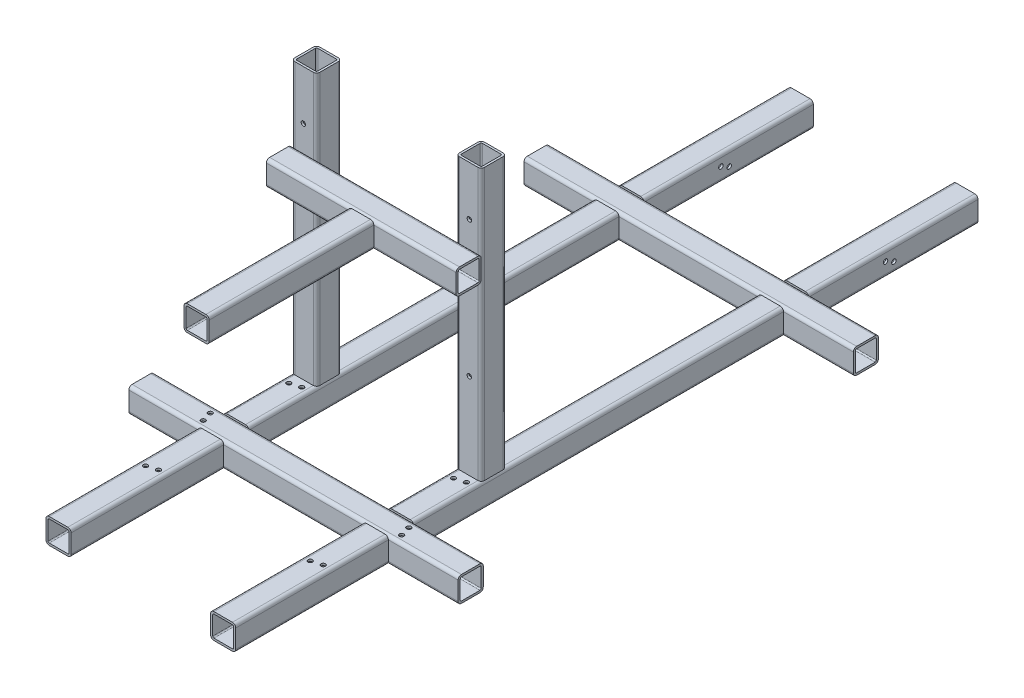
SolidWorks part; units mm, degrees
material "Alumina"
ref_plane "Front Plane" through (0, 0, 0) normal (0, 0, 1) x (1, 0, 0)
ref_plane "Top Plane" through (0, 0, 0) normal (0, 1, 0) x (1, 0, 0)
ref_plane "Right Plane" through (0, 0, 0) normal (1, 0, 0) x (0, 0, -1)
ref_plane "Bottom Face" through (0, 0, 0) normal (0, 1, 0) x (1, 0, 0)
ref_plane "Top Face" through (0, 38.1, 0) normal (0, 1, 0) x (1, 0, 0)
ref_plane "Mid Plane" through (0, 19.05, 0) normal (0, 1, 0) x (1, 0, 0)
ref_plane "Front Face" through (0, 0, 500) normal (0, 0, 1) x (1, 0, 0)
ref_plane "Back Face" through (0, 0, -500) normal (0, 0, 1) x (1, 0, 0)
ref_plane "Left Face" through (250, 0, 0) normal (1, 0, 0) x (0, 0, -1)
ref_plane "Right Face" through (-250, 0, 0) normal (1, 0, 0) x (0, 0, -1)
ref_plane "Divider Plane" through (0, 0, 140) normal (0, 0, 1) x (1, 0, 0)
ref_plane "Max Height Plane" through (0, 450, 0) normal (0, 1, 0) x (1, 0, 0)
ref_plane "Electronics Box Plane" through (0, 338.1, 0) normal (0, 1, 0) x (1, 0, 0)
sketch "Sketch2" plane through (250, 0, 0) normal (1, 0, 0) x (0, 0, -1)
  line L0 (330, 38.1) -> (-330, 38.1) construction
  line L5 (330, 0) -> (-330, 0) construction
  line L6 (0, 220) -> (0, -220) construction
  line L7 (-314.05, 38.1) -> (-285.95, 38.1)
  line L8 (-280.95, 33.1) -> (-280.95, 5)
  line L9 (-315.875, 33.1) -> (-315.875, 5)
  line L10 (-314.05, 3.175) -> (-285.95, 3.175)
  line L11 (-285.95, 0) -> (-314.05, 0)
  line L12 (-319.05, 5) -> (-319.05, 33.1)
  line L13 (-300, 38.1) -> (-300, 0) construction
  line L14 (-319.05, 19.05) -> (-280.95, 19.05) construction
  line L15 (-284.125, 5) -> (-284.125, 33.1)
  line L16 (-285.95, 34.925) -> (-314.05, 34.925)
  line L17 (-300, 34.925) -> (-300, 3.175) construction
  line L18 (-315.875, 19.05) -> (-284.125, 19.05) construction
  arc A0 (-285.95, 38.1) -> (-280.95, 33.1) centre (-285.95, 33.1) cw
  arc A1 (-280.95, 5) -> (-285.95, 0) centre (-285.95, 5) cw
  arc A2 (-314.05, 0) -> (-319.05, 5) centre (-314.05, 5) cw
  arc A3 (-319.05, 33.1) -> (-314.05, 38.1) centre (-314.05, 33.1) cw
  arc A4 (-315.875, 5) -> (-314.05, 3.175) centre (-314.05, 5) ccw
  arc A5 (-285.95, 3.175) -> (-284.125, 5) centre (-285.95, 5) ccw
  arc A6 (-284.125, 33.1) -> (-285.95, 34.925) centre (-285.95, 33.1) ccw
  arc A7 (-314.05, 34.925) -> (-315.875, 33.1) centre (-314.05, 33.1) ccw
  point P20 (-300, 19.05)
  point P39 (-300, 19.05)
  dimension "D1" = 5
  dimension "D2" = 300
  dimension "D3" = 3.175
extrude "Front Cross-Car Member" add sketch "Sketch2" against normal up to surface (500 mm away) up to plane "Right Face"
sketch "Sketch5" plane through (250, 0, 0) normal (1, 0, 0) x (0, 0, -1)
  line L0 (285.95, 38.1) -> (314.05, 38.1)
  line L1 (319.05, 33.1) -> (319.05, 5)
  line L2 (314.05, 0) -> (285.95, 0)
  line L3 (280.95, 5) -> (280.95, 33.1)
  line L4 (300, 38.1) -> (300, 0) construction
  line L5 (280.95, 19.05) -> (319.05, 19.05) construction
  line L6 (285.95, 34.925) -> (314.05, 34.925)
  line L7 (315.875, 33.1) -> (315.875, 5)
  line L8 (314.05, 3.175) -> (285.95, 3.175)
  line L9 (284.125, 5) -> (284.125, 33.1)
  line L10 (300, 34.925) -> (300, 3.175) construction
  line L11 (284.125, 19.05) -> (315.875, 19.05) construction
  line L12 (330, 0) -> (-330, 0) construction
  line L14 (330, 38.1) -> (-330, 38.1) construction
  line L15 (0, 220) -> (0, -220) construction
  arc A0 (314.05, 38.1) -> (319.05, 33.1) centre (314.05, 33.1) cw
  arc A1 (319.05, 5) -> (314.05, 0) centre (314.05, 5) cw
  arc A2 (285.95, 0) -> (280.95, 5) centre (285.95, 5) cw
  arc A3 (280.95, 33.1) -> (285.95, 38.1) centre (285.95, 33.1) cw
  arc A4 (314.05, 34.925) -> (315.875, 33.1) centre (314.05, 33.1) cw
  arc A5 (315.875, 5) -> (314.05, 3.175) centre (314.05, 5) cw
  arc A6 (285.95, 3.175) -> (284.125, 5) centre (285.95, 5) cw
  arc A7 (284.125, 33.1) -> (285.95, 34.925) centre (285.95, 33.1) cw
  point P32 (300, 19.05)
  point P33 (300, 19.05)
  dimension "D2" = 5
  dimension "D1" = 3.175
  dimension "D3" = 300
extrude "Back Cross-Car Member" add sketch "Sketch5" against normal up to surface (500 mm away) separate body up to plane "Right Face"
sketch "Sketch6" plane through (0, 0, -500) normal (0, 0, 1) x (1, 0, 0)
  line L0 (110.95, 38.1) -> (139.05, 38.1)
  line L1 (144.05, 33.1) -> (144.05, 5)
  line L2 (109.125, 33.1) -> (109.125, 5)
  line L3 (110.95, 3.175) -> (139.05, 3.175)
  line L4 (139.05, 0) -> (110.95, 0)
  line L5 (105.95, 5) -> (105.95, 33.1)
  line L6 (125, 38.1) -> (125, 0) construction
  line L7 (105.95, 19.05) -> (144.05, 19.05) construction
  line L8 (140.875, 5) -> (140.875, 33.1)
  line L9 (139.05, 34.925) -> (110.95, 34.925)
  line L10 (125, 34.925) -> (125, 3.175) construction
  line L11 (109.125, 19.05) -> (140.875, 19.05) construction
  line L12 (330, 38.1) -> (-330, 38.1) construction
  line L13 (330, 0) -> (-330, 0) construction
  line L14 (0, -220) -> (0, 220) construction
  arc A0 (139.05, 38.1) -> (144.05, 33.1) centre (139.05, 33.1) cw
  arc A1 (144.05, 5) -> (139.05, 0) centre (139.05, 5) cw
  arc A2 (110.95, 0) -> (105.95, 5) centre (110.95, 5) cw
  arc A3 (105.95, 33.1) -> (110.95, 38.1) centre (110.95, 33.1) cw
  arc A4 (109.125, 5) -> (110.95, 3.175) centre (110.95, 5) ccw
  arc A5 (139.05, 3.175) -> (140.875, 5) centre (139.05, 5) ccw
  arc A6 (140.875, 33.1) -> (139.05, 34.925) centre (139.05, 33.1) ccw
  arc A7 (110.95, 34.925) -> (109.125, 33.1) centre (110.95, 33.1) ccw
  point P16 (125, 19.05)
  point P33 (125, 19.05)
  dimension "D1" = 5
  dimension "D2" = 3.175
  dimension "D3" = 125
extrude "Back Left Along-Car Member" add sketch "Sketch6" along normal blind 180.95 and the other way blind 76.2
extrude "Middle Left Along-Car Member" add sketch "Sketch6<2>" along normal blind 561.9 from offset 219.05
sketch "Sketch6<2>" plane through (0, 0, -500) normal (0, 0, 1) x (1, 0, 0) same geometry as "Sketch6"
extrude "Front Left Along-Car Member" add sketch "Sketch6<3>" along normal blind 231.75 from offset 819.05
sketch "Sketch6<3>" plane through (0, 0, -500) normal (0, 0, 1) x (1, 0, 0) same geometry as "Sketch6"
sketch "Sketch7" plane through (0, 0, -500) normal (0, 0, 1) x (1, 0, 0)
  line L0 (-139.05, 38.1) -> (-110.95, 38.1)
  line L1 (-105.95, 33.1) -> (-105.95, 5)
  line L2 (-140.875, 33.1) -> (-140.875, 5)
  line L3 (-139.05, 3.175) -> (-110.95, 3.175)
  line L4 (-110.95, 0) -> (-139.05, 0)
  line L5 (-144.05, 5) -> (-144.05, 33.1)
  line L6 (-125, 38.1) -> (-125, 0) construction
  line L7 (-144.05, 19.05) -> (-105.95, 19.05) construction
  line L8 (-109.125, 5) -> (-109.125, 33.1)
  line L9 (-110.95, 34.925) -> (-139.05, 34.925)
  line L10 (-125, 34.925) -> (-125, 3.175) construction
  line L11 (-140.875, 19.05) -> (-109.125, 19.05) construction
  line L12 (330, 38.1) -> (-330, 38.1) construction
  line L13 (330, 0) -> (-330, 0) construction
  line L14 (0, -220) -> (0, 220) construction
  arc A0 (-110.95, 38.1) -> (-105.95, 33.1) centre (-110.95, 33.1) cw
  arc A1 (-105.95, 5) -> (-110.95, 0) centre (-110.95, 5) cw
  arc A2 (-139.05, 0) -> (-144.05, 5) centre (-139.05, 5) cw
  arc A3 (-144.05, 33.1) -> (-139.05, 38.1) centre (-139.05, 33.1) cw
  arc A4 (-140.875, 5) -> (-139.05, 3.175) centre (-139.05, 5) ccw
  arc A5 (-110.95, 3.175) -> (-109.125, 5) centre (-110.95, 5) ccw
  arc A6 (-109.125, 33.1) -> (-110.95, 34.925) centre (-110.95, 33.1) ccw
  arc A7 (-139.05, 34.925) -> (-140.875, 33.1) centre (-139.05, 33.1) ccw
  point P16 (-125, 19.05)
  point P33 (-125, 19.05)
  dimension "D1" = 5
  dimension "D2" = 3.175
  dimension "D3" = 125
extrude "Back Right Along-Car Member" add sketch "Sketch7" along normal blind 180.95 and the other way blind 76.2
extrude "Middle Right Along-Car Member" add sketch "Sketch7<2>" along normal blind 561.9 from offset 219.05
sketch "Sketch7<2>" plane through (0, 0, -500) normal (0, 0, 1) x (1, 0, 0) same geometry as "Sketch7"
extrude "Front Right Along-Car Member" add sketch "Sketch7<3>" along normal blind 231.75 from offset 819.05
sketch "Sketch7<3>" plane through (0, 0, -500) normal (0, 0, 1) x (1, 0, 0) same geometry as "Sketch7"
sketch "Sketch8" plane through (0, 38.1, 0) normal (0, 1, 0) x (1, 0, 0)
  line L0 (-139.05, -140) -> (-110.95, -140)
  line L1 (-105.95, -145) -> (-105.95, -173.1)
  line L2 (-140.875, -145) -> (-140.875, -173.1)
  line L3 (-139.05, -174.925) -> (-110.95, -174.925)
  line L4 (-110.95, -178.1) -> (-139.05, -178.1)
  line L5 (-144.05, -173.1) -> (-144.05, -145)
  line L6 (-125, -140) -> (-125, -178.1) construction
  line L7 (-144.05, -159.05) -> (-105.95, -159.05) construction
  line L8 (-109.125, -173.1) -> (-109.125, -145)
  line L9 (-110.95, -143.175) -> (-139.05, -143.175)
  line L10 (-125, -143.175) -> (-125, -174.925) construction
  line L11 (-140.875, -159.05) -> (-109.125, -159.05) construction
  line L12 (-220, -140) -> (220, -140) construction
  line L13 (0, -247.5) -> (0, 247.5) construction
  arc A0 (-110.95, -140) -> (-105.95, -145) centre (-110.95, -145) cw
  arc A1 (-105.95, -173.1) -> (-110.95, -178.1) centre (-110.95, -173.1) cw
  arc A2 (-139.05, -178.1) -> (-144.05, -173.1) centre (-139.05, -173.1) cw
  arc A3 (-144.05, -145) -> (-139.05, -140) centre (-139.05, -145) cw
  arc A4 (-140.875, -173.1) -> (-139.05, -174.925) centre (-139.05, -173.1) ccw
  arc A5 (-110.95, -174.925) -> (-109.125, -173.1) centre (-110.95, -173.1) ccw
  arc A6 (-109.125, -145) -> (-110.95, -143.175) centre (-110.95, -145) ccw
  arc A7 (-139.05, -143.175) -> (-140.875, -145) centre (-139.05, -145) ccw
  point P16 (-125, -159.05)
  point P33 (-125, -159.05)
  dimension "D1" = 5
  dimension "D2" = 3.175
  dimension "D3" = 38.1
  dimension "D4" = 125
extrude "Right Vertical Member" add sketch "Sketch8" along normal up to surface (411.9 mm away) up to plane "Max Height Plane"
sketch "Sketch10" plane through (0, 38.1, 0) normal (0, 1, 0) x (1, 0, 0)
  line L0 (110.95, -140) -> (139.05, -140)
  line L1 (144.05, -145) -> (144.05, -173.1)
  line L2 (109.125, -145) -> (109.125, -173.1)
  line L3 (110.95, -174.925) -> (139.05, -174.925)
  line L4 (139.05, -178.1) -> (110.95, -178.1)
  line L5 (105.95, -173.1) -> (105.95, -145)
  line L6 (125, -140) -> (125, -178.1) construction
  line L7 (105.95, -159.05) -> (144.05, -159.05) construction
  line L8 (140.875, -173.1) -> (140.875, -145)
  line L9 (139.05, -143.175) -> (110.95, -143.175)
  line L10 (125, -143.175) -> (125, -174.925) construction
  line L11 (109.125, -159.05) -> (140.875, -159.05) construction
  line L12 (-220, -140) -> (220, -140) construction
  line L13 (0, -247.5) -> (0, 247.5) construction
  arc A0 (139.05, -140) -> (144.05, -145) centre (139.05, -145) cw
  arc A1 (144.05, -173.1) -> (139.05, -178.1) centre (139.05, -173.1) cw
  arc A2 (110.95, -178.1) -> (105.95, -173.1) centre (110.95, -173.1) cw
  arc A3 (105.95, -145) -> (110.95, -140) centre (110.95, -145) cw
  arc A4 (109.125, -173.1) -> (110.95, -174.925) centre (110.95, -173.1) ccw
  arc A5 (139.05, -174.925) -> (140.875, -173.1) centre (139.05, -173.1) ccw
  arc A6 (140.875, -145) -> (139.05, -143.175) centre (139.05, -145) ccw
  arc A7 (110.95, -143.175) -> (109.125, -145) centre (110.95, -145) ccw
  point P16 (125, -159.05)
  point P33 (125, -159.05)
  dimension "D1" = 5
  dimension "D2" = 3.175
  dimension "D3" = 38.1
  dimension "D4" = 125
extrude "Left Vertical Member" add sketch "Sketch10" along normal up to surface (411.9 mm away) up to plane "Max Height Plane"
sketch "Sketch11" plane through (250, 0, 0) normal (1, 0, 0) x (0, 0, -1)
  line L0 (-211.2, 338.1) -> (-183.1, 338.1)
  line L1 (-178.1, 333.1) -> (-178.1, 305)
  line L2 (-213.025, 333.1) -> (-213.025, 305)
  line L3 (-211.2, 303.175) -> (-183.1, 303.175)
  line L4 (-183.1, 300) -> (-211.2, 300)
  line L5 (-216.2, 305) -> (-216.2, 333.1)
  line L6 (-197.15, 338.1) -> (-197.15, 300) construction
  line L7 (-216.2, 319.05) -> (-178.1, 319.05) construction
  line L8 (-181.275, 305) -> (-181.275, 333.1)
  line L9 (-183.1, 334.925) -> (-211.2, 334.925)
  line L10 (-197.15, 334.925) -> (-197.15, 303.175) construction
  line L11 (-213.025, 319.05) -> (-181.275, 319.05) construction
  line L12 (-140, 220) -> (-140, -220) construction
  line L13 (330, 338.1) -> (-330, 338.1) construction
  arc A0 (-183.1, 338.1) -> (-178.1, 333.1) centre (-183.1, 333.1) cw
  arc A1 (-178.1, 305) -> (-183.1, 300) centre (-183.1, 305) cw
  arc A2 (-211.2, 300) -> (-216.2, 305) centre (-211.2, 305) cw
  arc A3 (-216.2, 333.1) -> (-211.2, 338.1) centre (-211.2, 333.1) cw
  arc A4 (-213.025, 305) -> (-211.2, 303.175) centre (-211.2, 305) ccw
  arc A5 (-183.1, 303.175) -> (-181.275, 305) centre (-183.1, 305) ccw
  arc A6 (-181.275, 333.1) -> (-183.1, 334.925) centre (-183.1, 333.1) ccw
  arc A7 (-211.2, 334.925) -> (-213.025, 333.1) centre (-211.2, 333.1) ccw
  point P16 (-197.15, 319.05)
  point P33 (-197.15, 319.05)
  dimension "D1" = 5
  dimension "D2" = 3.175
  dimension "D3" = 38.1
  dimension "D4" = 38.1
extrude "Upper Cross-Car Member" add sketch "Sketch11" against normal blind 288.1 from offset 105.95 offset against normal yes
sketch "Sketch12" plane through (0, 0, 140) normal (0, 0, 1) x (1, 0, 0)
  line L0 (-14.05, 338.1) -> (14.05, 338.1)
  line L1 (19.05, 333.1) -> (19.05, 305)
  line L2 (-15.875, 333.1) -> (-15.875, 305)
  line L3 (-14.05, 303.175) -> (14.05, 303.175)
  line L4 (14.05, 300) -> (-14.05, 300)
  line L5 (-19.05, 305) -> (-19.05, 333.1)
  line L6 (0, 338.1) -> (0, 300) construction
  line L7 (-19.05, 319.05) -> (19.05, 319.05) construction
  line L8 (15.875, 305) -> (15.875, 333.1)
  line L9 (14.05, 334.925) -> (-14.05, 334.925)
  line L10 (0, 334.925) -> (0, 303.175) construction
  line L11 (-15.875, 319.05) -> (15.875, 319.05) construction
  line L12 (330, 338.1) -> (-330, 338.1) construction
  line L13 (0, -247.5) -> (0, 247.5) construction
  arc A0 (14.05, 338.1) -> (19.05, 333.1) centre (14.05, 333.1) cw
  arc A1 (19.05, 305) -> (14.05, 300) centre (14.05, 305) cw
  arc A2 (-14.05, 300) -> (-19.05, 305) centre (-14.05, 305) cw
  arc A3 (-19.05, 333.1) -> (-14.05, 338.1) centre (-14.05, 333.1) cw
  arc A4 (-15.875, 305) -> (-14.05, 303.175) centre (-14.05, 305) ccw
  arc A5 (14.05, 303.175) -> (15.875, 305) centre (14.05, 305) ccw
  arc A6 (15.875, 333.1) -> (14.05, 334.925) centre (14.05, 333.1) ccw
  arc A7 (-14.05, 334.925) -> (-15.875, 333.1) centre (-14.05, 333.1) ccw
  point P16 (0, 319.05)
  point P33 (0, 319.05)
  dimension "D1" = 5
  dimension "D2" = 3.175
  dimension "D3" = 38.1
extrude "E-Box Platform Base" add sketch "Sketch12" along normal blind 250 from offset 76.2
sketch "Sketch13" plane through (0, 0, 140) normal (0, 0, -1) x (-1, 0, 0)
  circle A0 centre (-126, 375) radius 3.3782
  circle A1 centre (126, 375) radius 3.3782
  circle A2 centre (126.05, 168.6) radius 3.3782
  circle A3 centre (-125.95, 168.6) radius 3.3782
extrude "Cut-Extrude1" cut sketch "Sketch13" against normal up to surface (38.1 mm away) up to face at (125, 171.55, 178.1)
sketch "Sketch14" plane through (0, 38.1, 0) normal (0, 1, 0) x (1, 0, 0)
  circle A0 centre (-132.62, -411) radius 3.3782
  circle A1 centre (-117.38, -406.6) radius 3.3782
  circle A2 centre (-152.9, -292.48) radius 3.3782
  circle A3 centre (-148.5, -307.72) radius 3.3782
  circle A6 centre (117.38, -193.6) radius 3.3782
  circle A7 centre (132.62, -189.2) radius 3.3782
  circle A8 centre (152.9, -307.72) radius 3.3782
  circle A9 centre (148.5, -292.48) radius 3.3782
  circle A10 centre (117.38, -411) radius 3.3782
  circle A11 centre (132.62, -406.6) radius 3.3782
  circle A12 centre (-132.62, -193.6) radius 3.3782
  circle A13 centre (-117.38, -189.2) radius 3.3782
extrude "Cut-Extrude2" cut sketch "Sketch14" against normal up to surface (38.1 mm away) up to face at (125, 0, 434.925)
sketch "Sketch16" plane through (105.95, 0, 0) normal (-1, 0, 0) x (0, 0, 1)
  circle A0 centre (-448.5, 15.24) radius 3.3782
  circle A1 centre (-435.8, 21.59) radius 3.3782
extrude "Cut-Extrude4" cut sketch "Sketch16" along normal up to surface and the other way up to surface up to face at (-144.05, 19.05, -447.625) other way up to face at (144.05, 19.05, -447.625)
equation "\"D1@Front Face\" = \"frameLength@Master Assembly.SLDASM\" / 2"
equation "\"D1@Back Face\" = \"frameLength@Master Assembly.SLDASM\" / 2"
equation "\"D1@Left Face\"=\"frameWidth@Master Assembly.SLDASM\"/2"
equation "\"D1@Right Face\" = \"frameWidth@Master Assembly.SLDASM\" / 2"
equation "\"D1@Top Face\"=\"frameTubeStockHeight@Master Assembly.SLDASM\""
equation "\"D2@Sketch2\"=\"frameMemberDistLength@Master Assembly.SLDASM\"/2"
equation "\"D3@Sketch2\"=\"frameTubeStockWallThickness@Master Assembly.SLDASM\""
equation "\"D1@Sketch5\"=\"frameTubeStockWallThickness@Master Assembly.SLDASM\""
equation "\"D3@Sketch5\"=\"frameMemberDistLength@Master Assembly.SLDASM\"/2"
equation "\"D3@Sketch6\"=\"frameMemberDistWidth@Master Assembly.SLDASM\"/2"
equation "\"D1@Back Left Along-Car Member\"=( \"frameLength@Master Assembly.Assembly\" - \"frameMemberDistLength@Master Assembly.Assembly\" - \"frameTubeStockHeight@Master Assembly.Assembly\" )  / 2"
equation "\"D19@Middle Left Along-Car Member\" = ( \"frameLength@Master Assembly.SLDASM\" - \"frameMemberDistLength@Master Assembly.SLDASM\" + \"frameTubeStockHeight@Master Assembly.SLDASM\" ) / 2"
equation "\"D1@Middle Left Along-Car Member\"=\"frameMemberDistLength@Master Assembly.SLDASM\" - \"frameTubeStockHeight@Master Assembly.SLDASM\""
equation "\"D19@Front Left Along-Car Member\"=( \"frameLength@Master Assembly.SLDASM\" - \"frameMemberDistLength@Master Assembly.SLDASM\" )  / 2 + \"frameMemberDistLength@Master Assembly.SLDASM\" + \"frameTubeStockHeight@Master Assembly.SLDASM\" / 2"
equation "\"D1@Front Left Along-Car Member\" =  ( \"frameLength@Master Assembly.Assembly\" - \"frameMemberDistLength@Master Assembly.Assembly\" - \"frameTubeStockHeight@Master Assembly.Assembly\" )  / 2 + 2in"
equation "\"D3@Sketch7\"=\"frameMemberDistWidth@Master Assembly.SLDASM\"/2"
equation "\"D1@Back Right Along-Car Member\"=(\"frameLength@Master Assembly.SLDASM\" - \"frameMemberDistLength@Master Assembly.SLDASM\" - \"frameTubeStockHeight@Master Assembly.SLDASM\")  / 2"
equation "\"D19@Middle Right Along-Car Member\" = ( \"frameLength@Master Assembly.SLDASM\" - \"frameMemberDistLength@Master Assembly.SLDASM\" + \"frameTubeStockHeight@Master Assembly.SLDASM\" ) / 2"
equation "\"D1@Middle Right Along-Car Member\"=\"frameMemberDistLength@Master Assembly.SLDASM\" - \"frameTubeStockHeight@Master Assembly.SLDASM\""
equation "\"D19@Front Right Along-Car Member\"=( \"frameLength@Master Assembly.SLDASM\" - \"frameMemberDistLength@Master Assembly.SLDASM\" )  / 2 + \"frameMemberDistLength@Master Assembly.SLDASM\" + \"frameTubeStockHeight@Master Assembly.SLDASM\" / 2"
equation "\"D1@Front Right Along-Car Member\"=( \"frameLength@Master Assembly.Assembly\" - \"frameMemberDistLength@Master Assembly.Assembly\" - \"frameTubeStockHeight@Master Assembly.Assembly\" )  / 2 + 2in"
equation "\"D1@Divider Plane\"= \"frameDividerPlaneOffset@Master Assembly.SLDASM\""
equation "\"D3@Sketch8\"=\"frameTubeStockHeight@Master Assembly.SLDASM\""
equation "\"D4@Sketch8\"=\"frameMemberDistWidth@Master Assembly.SLDASM\"/2"
equation "\"D1@Max Height Plane\" = \"frameHeight@Master Assembly.SLDASM\""
equation "\"D4@Sketch10\"=\"frameMemberDistWidth@Master Assembly.SLDASM\"/2"
equation "\"D1@Electronics Box Plane\" = \"eboxPlaneHeight@Master Assembly.SLDASM\""
equation "\"D4@Sketch11\"=\"frameTubeStockHeight@Master Assembly.SLDASM\""
equation "\"D19@Upper Cross-Car Member\" = ( \"frameWidth@Master Assembly.SLDASM\" - \"frameMemberDistWidth@Master Assembly.SLDASM\" - \"frameTubeStockHeight@Master Assembly.SLDASM\" ) / 2"
equation "\"D1@Upper Cross-Car Member\" = \"frameMemberDistWidth@Master Assembly.SLDASM\" + \"frameTubeStockHeight@Master Assembly.SLDASM\""
equation "\"D19@E-Box Platform Base\"= \"frameTubeStockHeight@Master Assembly.SLDASM\" * 2"
equation "\"D2@Sketch6\"=\"frameTubeStockWallThickness@Master Assembly.SLDASM\""
equation "\"D2@Sketch7\"=\"frameTubeStockWallThickness@Master Assembly.SLDASM\""
equation "\"D2@Sketch8\"=\"frameTubeStockWallThickness@Master Assembly.SLDASM\""
equation "\"D3@Sketch10\"=\"frameTubeStockHeight@Master Assembly.SLDASM\""
equation "\"D2@Sketch10\"=\"frameTubeStockWallThickness@Master Assembly.SLDASM\""
equation "\"D3@Sketch11\"=\"frameTubeStockHeight@Master Assembly.SLDASM\""
equation "\"D2@Sketch11\"=\"frameTubeStockWallThickness@Master Assembly.SLDASM\""
equation "\"D3@Sketch12\"=\"frameTubeStockHeight@Master Assembly.SLDASM\""
equation "\"D2@Sketch12\"=\"frameTubeStockWallThickness@Master Assembly.SLDASM\""
